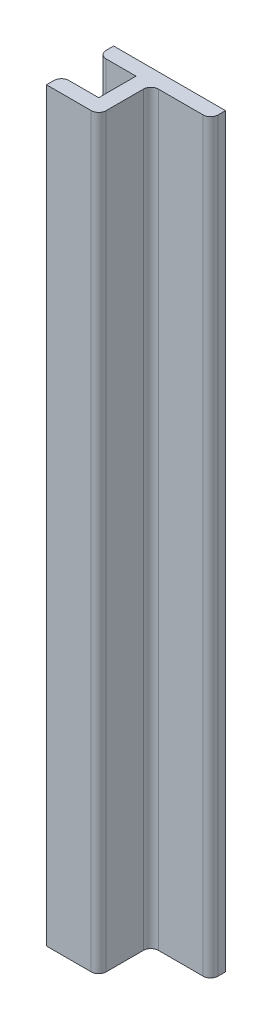
SolidWorks part; units mm, degrees
ref_plane "Front Plane" through (0, 0, 0) normal (0, 0, 1) x (1, 0, 0)
ref_plane "Top Plane" through (0, 0, 0) normal (0, 1, 0) x (1, 0, 0)
ref_plane "Right Plane" through (0, 0, 0) normal (1, 0, 0) x (0, 0, -1)
sketch "Sketch1" plane through (0, 0, 0) normal (0, 1, 0) x (1, 0, 0)
  line L0 (-24.9296, 0) -> (27.7465, 0) construction
  line L1 (0, -18.0986) -> (0, -7) construction
  line L2 (0, 0) -> (15, 0)
  line L3 (15, 0) -> (15, -2)
  line L4 (15, -2) -> (7, -2)
  line L5 (7, -2) -> (7, -9)
  line L6 (7, -9) -> (0, -9)
  line L7 (0, -9) -> (0, -7)
  line L8 (0, -7) -> (5, -7)
  line L9 (5, -7) -> (5, -2)
  line L10 (5, -2) -> (0, -2)
  line L11 (0, -2) -> (0, 18.662) construction
  line L12 (0, -2) -> (0, 0)
  dimension "D1" = 15
  dimension "D2" = 2
  dimension "D3" = 2
  dimension "D4" = 5
  dimension "D5" = 2
  dimension "D6" = 2
  dimension "D7" = 5
extrude "Boss-Extrude1" add sketch "Sketch1" along normal blind 100
fillet "Fillet1" radius 1 5 edges at (0, 50, 7) (0, 50, 2) (7, 50, 9) (7, 50, 2) (15, 50, 2)
